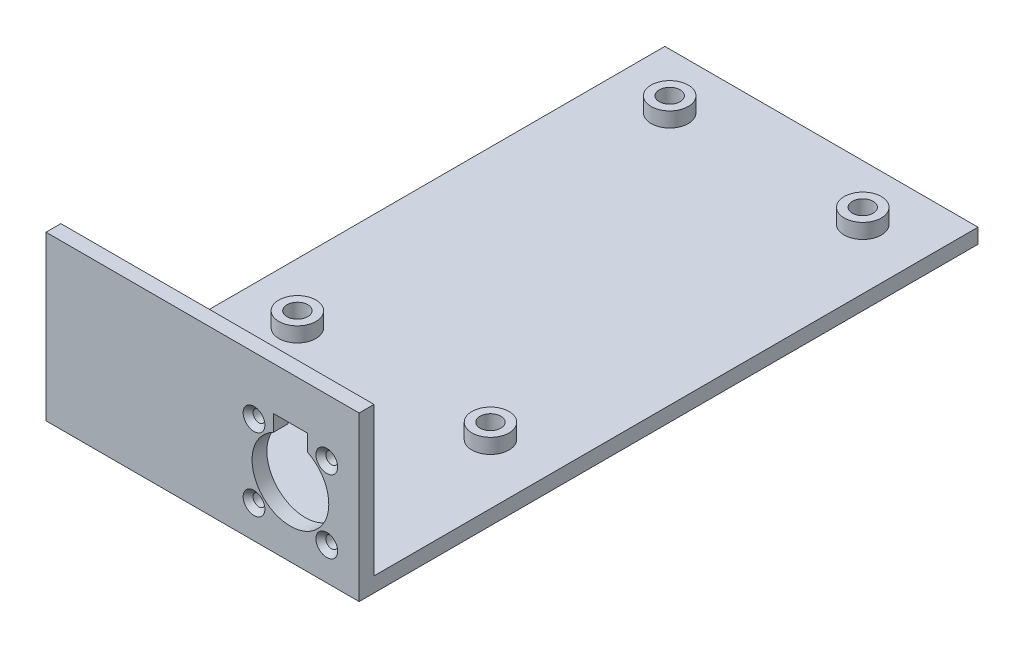
SolidWorks part; units mm, degrees
ref_plane "Спереди" through (0, 0, 0) normal (0, 0, 1) x (1, 0, 0)
ref_plane "Сверху" through (0, 0, 0) normal (0, 1, 0) x (1, 0, 0)
ref_plane "Справа" through (0, 0, 0) normal (1, 0, 0) x (0, 0, -1)
sketch "Эскиз2" plane through (0, 0, 0) normal (0, -1, 0) x (1, 0, 0)
  circle A0 centre (19.5, 37.6) radius 3.75
  circle A1 centre (19.5, -37.6) radius 3.75
  circle A2 centre (-19.5, -37.6) radius 3.75
  circle A3 centre (-19.5, 37.6) radius 3.75
  dimension "D1" = 7.5
extrude "Бобышка-Вытянуть1" add sketch "Эскиз2" along normal blind 3
sketch "Эскиз3" plane through (0, -3, 0) normal (0, -1, 0) x (1, 0, 0)
  line L0 (26.625, 41.25) -> (26.625, -41.25) construction
  line L1 (-31.625, 76.25) -> (31.625, 76.25)
  line L2 (-31.625, 76.25) -> (-31.625, -48.75)
  line L3 (-31.625, -48.75) -> (31.625, -48.75)
  line L4 (31.625, 76.25) -> (31.625, -48.75)
  line L5 (-31.625, 76.25) -> (31.625, -48.75) construction
  line L6 (-31.625, -48.75) -> (31.625, 76.25) construction
  line L8 (-23.625, 41.25) -> (23.625, 41.25) construction
  line L9 (-26.625, 41.25) -> (-26.625, -41.25) construction
  point P0 (0, 13.75)
  dimension "D1" = 5
  dimension "D2" = 125
  dimension "D3" = 35
  dimension "D4" = 5
extrude "Бобышка-Вытянуть2" add sketch "Эскиз3" along normal blind 3
sketch "Эскиз4" plane through (0, 0, 0) normal (0, 1, 0) x (1, 0, 0)
  circle A0 centre (19.5, 37.6) radius 2.1
  circle A1 centre (19.5, -37.6) radius 2.1
  circle A2 centre (-19.5, -37.6) radius 2.1
  circle A3 centre (-19.5, 37.6) radius 2.1
  dimension "D1" = 4.2
extrude "Вырез-Вытянуть1" cut sketch "Эскиз4" against normal blind 4
sketch "Эскиз5" plane through (0, -3, 0) normal (0, 1, 0) x (1, 0, 0)
  line L0 (31.625, 48.75) -> (31.625, -76.25) construction
  line L1 (-31.625, -76.25) -> (31.625, -76.25)
  line L2 (-31.625, -76.25) -> (-31.625, -73.25)
  line L3 (-31.625, -73.25) -> (31.625, -73.25)
  line L4 (31.625, -76.25) -> (31.625, -73.25)
  dimension "D1" = 3
extrude "Бобышка-Вытянуть3" add sketch "Эскиз5" along normal blind 30
sketch "Эскиз8" plane through (0, 0, 76.25) normal (0, 0, 1) x (1, 0, 0)
  line L6 (21.1931, 14.9397) -> (21.1931, 18.25)
  line L7 (21.1931, 18.25) -> (14.2931, 18.25)
  line L8 (14.2931, 18.25) -> (14.2931, 14.9397)
  line L9 (21.1931, 14.9397) -> (21.1931, 18.25)
  line L10 (21.1931, 18.25) -> (14.2931, 18.25)
  line L11 (14.2931, 18.25) -> (14.2931, 14.9397)
  arc A2 (14.2931, 14.9397) -> (21.1931, 14.9397) centre (17.7431, 8) ccw
  arc A3 (14.2931, 14.9397) -> (21.1931, 14.9397) centre (17.7431, 8) ccw
  dimension "D1" = 0.15
extrude "Вырез-Вытянуть2" cut sketch "Эскиз8" against normal blind 10
hole_wizard "Зенковка для винта с полупотайной головкой M21" positions "Эскиз9" profile "Эскиз11" countersink size "M2" standard "DIN"
sketch "Эскиз9" plane through (0, 0, 76.25) normal (0, 0, 1) x (1, 0, 0)
  circle A0 centre (10.3931, 0.65) radius 1.2 construction
  circle A1 centre (25.0931, 0.65) radius 1.2 construction
  circle A2 centre (10.3931, 15.35) radius 1.2 construction
  circle A3 centre (25.0931, 15.35) radius 1.2 construction
  circle A4 centre (10.3931, 0.65) radius 1.2 construction
  circle A5 centre (25.0931, 0.65) radius 1.2 construction
  circle A6 centre (10.3931, 15.35) radius 1.2 construction
  circle A7 centre (25.0931, 15.35) radius 1.2 construction
  point P1 (10.3931, 0.65)
  point P3 (25.0931, 0.65)
  point P5 (10.3931, 15.35)
  point P7 (25.0931, 15.35)
sketch "Эскиз11" plane through (10.3931, 0.65, 76.25) normal (1, 0, 0) x (0, -1, 0)
  line L0 (0, 0) -> (0, 5.721)
  line L1 (0, 5.721) -> (1.2, 5)
  line L2 (1.2, 5) -> (1.2, 1)
  line L3 (1.2, 1) -> (2.2, 0)
  line L5 (2.2, 0) -> (0, 0)
  line L6 (-1.2, 1) -> (-2.2, 0) construction
  line L10 (0, 5.721) -> (-1.2, 5) construction
  line L11 (0, -6.35) -> (0, 107.95) construction
  dimension "Диаметр отверстия" = 2.4
  dimension "Глубина отверстия" = 5
  dimension "Диаметр передней зенковки" = 4.4
  dimension "Угол передней зенковки" = 90
  dimension "Угол заточки сверла" = 118
